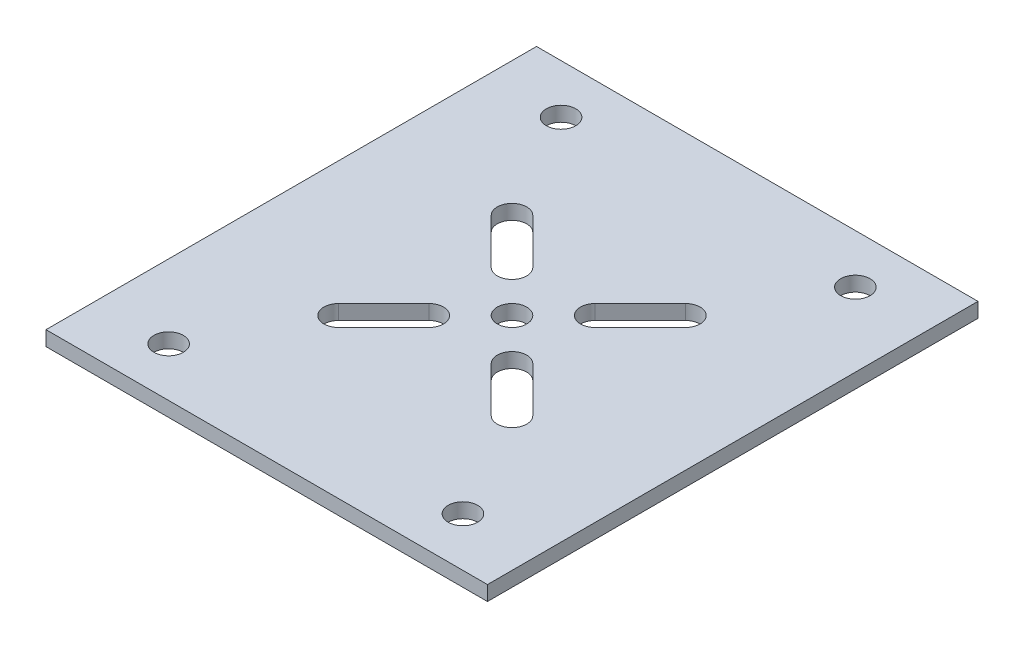
SolidWorks part; units mm, degrees
material "Thornel Mat VMA"
ref_plane "Front Plane" through (0, 0, 0) normal (0, 0, 1) x (1, 0, 0)
ref_plane "Top Plane" through (0, 0, 0) normal (0, 1, 0) x (1, 0, 0)
ref_plane "Right Plane" through (0, 0, 0) normal (1, 0, 0) x (0, 0, -1)
sketch "Sketch2" plane through (0, 0, 0) normal (0, 1, 0) x (1, 0, 0)
  line L1 (-22.5, -25) -> (22.5, -25)
  line L2 (-22.5, -25) -> (-22.5, 25)
  line L3 (-22.5, 25) -> (22.5, 25)
  line L4 (22.5, -25) -> (22.5, 25)
  point P0 (0, 0)
  dimension "D1" = 50
  dimension "D2" = 45
  dimension "D3" = 22.5
  dimension "D4" = 25
extrude "Boss-Extrude1" add sketch "Sketch2" along normal blind 1.5
sketch "Sketch3" plane through (0, 1.5, 0) normal (0, 1, 0) x (1, 0, 0)
  line L0 (-8.8388, 8.8388) -> (-4.2426, 4.2426) construction
  line L1 (-7.7782, 9.8995) -> (-3.182, 5.3033)
  line L2 (-9.8995, 7.7782) -> (-5.3033, 3.182)
  line L3 (-8.8388, -8.8388) -> (-4.2426, -4.2426) construction
  line L4 (-9.8995, -7.7782) -> (-5.3033, -3.182)
  line L5 (-7.7782, -9.8995) -> (-3.182, -5.3033)
  line L6 (8.8388, -8.8388) -> (4.2426, -4.2426) construction
  line L7 (7.7782, -9.8995) -> (3.182, -5.3033)
  line L8 (9.8995, -7.7782) -> (5.3033, -3.182)
  line L9 (8.8388, 8.8388) -> (4.2426, 4.2426) construction
  line L10 (9.8995, 7.7782) -> (5.3033, 3.182)
  line L11 (7.7782, 9.8995) -> (3.182, 5.3033)
  line L13 (-22.5, -25) -> (22.5, -25) construction
  line L14 (22.5, -25) -> (22.5, 25) construction
  line L16 (0, 0) -> (0, 25) construction
  circle A0 centre (0, 0) radius 1.5
  arc A1 (-7.7782, 9.8995) -> (-9.8995, 7.7782) centre (-8.8388, 8.8388) ccw
  arc A2 (-5.3033, 3.182) -> (-3.182, 5.3033) centre (-4.2426, 4.2426) ccw
  arc A3 (-9.8995, -7.7782) -> (-7.7782, -9.8995) centre (-8.8388, -8.8388) ccw
  arc A4 (-3.182, -5.3033) -> (-5.3033, -3.182) centre (-4.2426, -4.2426) ccw
  arc A5 (7.7782, -9.8995) -> (9.8995, -7.7782) centre (8.8388, -8.8388) ccw
  arc A6 (5.3033, -3.182) -> (3.182, -5.3033) centre (4.2426, -4.2426) ccw
  arc A7 (9.8995, 7.7782) -> (7.7782, 9.8995) centre (8.8388, 8.8388) ccw
  arc A8 (3.182, 5.3033) -> (5.3033, 3.182) centre (4.2426, 4.2426) ccw
  point P5 (-6.5407, 6.5407)
  point P15 (-6.5407, -6.5407)
  point P22 (6.5407, -6.5407)
  point P29 (6.5407, 6.5407)
  point P34 (0, 0)
  point P37 (0, -25)
  dimension "D1" = 3
  dimension "D2" = 1.5
  dimension "D4" = 12.5
  dimension "D6" = 25
  dimension "D7" = 22.5
  dimension "D9" = 6
  dimension "D3" = 6
  dimension "D10" = 12.5
  dimension "D8" = 45
  dimension "D5" = 4
extrude "Cut-Extrude1" cut sketch "Sketch3" against normal through all
sketch "Sketch4" plane through (0, 1.5, 0) normal (0, 1, 0) x (1, 0, 0)
  line L0 (14.1, 18.8) -> (15, 20) construction
  line L1 (14.1, -18.8) -> (15, -20) construction
  line L5 (-15, -20) -> (-14.1, -18.8) construction
  line L6 (-15, 20) -> (-14.1, 18.8) construction
  circle A0 centre (15, -20) radius 1.5
  circle A1 centre (-15, -20) radius 1.5
  circle A2 centre (15, 20) radius 1.5
  circle A3 centre (-15, 20) radius 1.5
  point P0 (0, 0)
  dimension "D3" = 3
  dimension "D4" = 3
  dimension "D5" = 3
  dimension "D6" = 3
  dimension "D1" = 30
  dimension "D2" = 40
extrude "Cut-Extrude2" cut sketch "Sketch4" against normal through all
